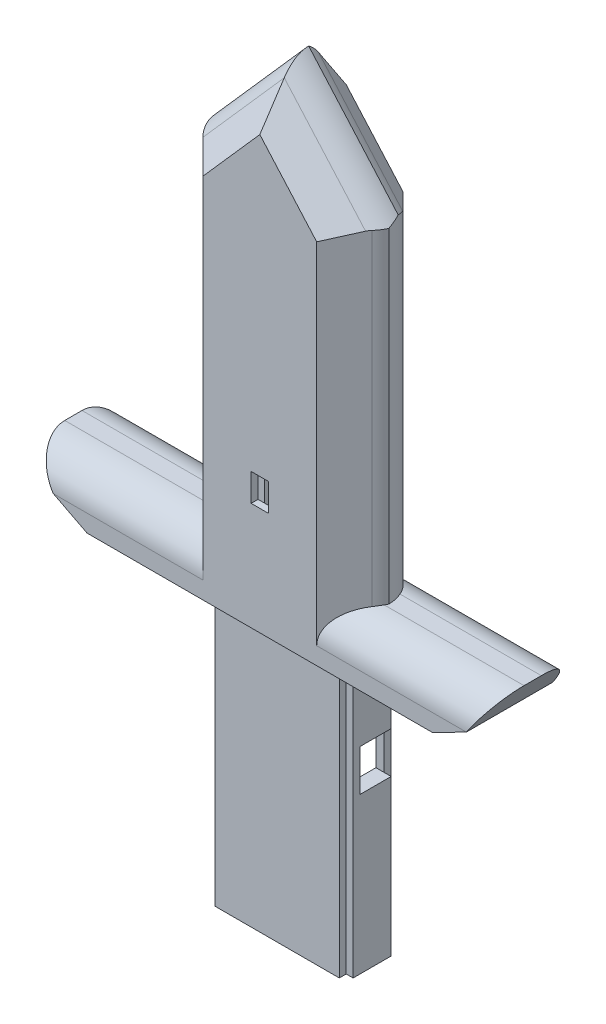
SolidWorks part; units mm, degrees
ref_plane "前视基准面" through (0, 0, 0) normal (0, 0, 1) x (1, 0, 0)
ref_plane "上视基准面" through (0, 0, 0) normal (0, 1, 0) x (1, 0, 0)
ref_plane "右视基准面" through (0, 0, 0) normal (1, 0, 0) x (0, 0, -1)
other "Configuration Table"
sketch "草图1" plane through (0, 0, 0) normal (0, 0, 1) x (1, 0, 0)
  line L0 (0, -55) -> (0, 55) construction
  line L1 (0, 200) -> (-26.4575, 170)
  line L2 (-26.4575, 170) -> (-26.4575, 75)
  line L3 (-26.4575, 75) -> (-66.4575, 75)
  line L4 (-66.4575, 75) -> (-59.7843, 65.0266)
  line L5 (-59.7843, 65.0266) -> (-50, 60)
  line L7 (-50, 60) -> (-20, 60)
  line L9 (-20, 60) -> (-20, -20)
  line L10 (-20, -20) -> (20, -20)
  line L11 (0, 200) -> (0, -20)
  line L15 (-26.4575, 170) -> (26.4575, 170) construction
  line L18 (20, 60) -> (20, -20)
  line L19 (50, 60) -> (20, 60)
  line L20 (59.7843, 65.0266) -> (50, 60)
  line L21 (66.4575, 75) -> (59.7843, 65.0266)
  line L22 (26.4575, 75) -> (66.4575, 75)
  line L23 (26.4575, 170) -> (26.4575, 75)
  line L24 (0, 200) -> (26.4575, 170)
  point P18 (0, 170)
  dimension "D1" = 80
  dimension "D2" = 20
  dimension "D3" = 220
  dimension "D4" = 40
  dimension "D5" = 95
  dimension "D6" = 15
  dimension "D7" = 30
  dimension "D8" = 40
  dimension "D9" = 12
  dimension "D10" = 11
  dimension "D11" = 20
extrude "凸台-拉伸1" add sketch "草图1" along normal blind 15 contours L1 L15 L11 | L11 L15 L24 | L15 L2 L3 L4 L5 L7 L9 L10 L11 | L15 L11 L10 L18 L19 L20 L21 L22 L23
sketch "草图2" plane through (0, 0, 0) normal (0, 0, -1) x (-1, 0, 0)
  line L0 (0, 81.7011) -> (-15, 66.7011)
  line L1 (-15, 66.7011) -> (0, 51.7011)
  line L2 (0, 51.7011) -> (15, 66.7011)
  line L3 (15, 66.7011) -> (0, 81.7011)
  dimension "D1" = 30
  dimension "D4" = 51.7011
extrude "切除-拉伸4" cut sketch "草图2" against normal through all
sketch "草图4" plane through (0, 0, 0) normal (0, 0, -1) x (-1, 0, 0)
  line L0 (-15, 66.7011) -> (-15, -15)
  line L1 (-15, -15) -> (15, -15)
  line L2 (15, -15) -> (15, 66.7011)
  line L3 (20, -20) -> (-20, -20) construction
  line M6 (15, 66.7011) -> (0, 51.7011)
  line M7 (0, 51.7011) -> (-15, 66.7011)
  dimension "D1" = 5
extrude "切除-拉伸5" cut sketch "草图4" against normal blind 5 and the other way through all contours L1 L2 L0 M6 M7
sketch "草图5" plane through (0, 0, 0) normal (0, 0, 1) x (1, 0, 0)
  line L0 (0, 200) -> (26.4575, 170)
  line L1 (26.4575, 170) -> (26.4575, 75)
  line L2 (26.4575, 75) -> (66.4575, 75)
  line L3 (66.4575, 75) -> (59.7843, 65.0266)
  line L4 (59.7843, 65.0266) -> (50, 60)
  line L5 (50, 60) -> (20, 60)
  line L6 (20, 60) -> (-20, 60)
  line L7 (-20, 60) -> (-50, 60)
  line L8 (-50, 60) -> (-59.7843, 65.0266)
  line L9 (-59.7843, 65.0266) -> (-66.4575, 75)
  line L10 (-66.4575, 75) -> (-26.4575, 75)
  line L11 (-26.4575, 75) -> (-26.4575, 170)
  line L12 (-26.4575, 170) -> (0, 200)
extrude "凸台-拉伸2" add sketch "草图5" against normal blind 5
sketch "草图7" plane through (0, 0, 0) normal (0, 0, 1) x (1, 0, 0)
  line L0 (0, 81.7011) -> (-15, 66.7011)
  line L1 (-15, 66.7011) -> (-15, 60)
  line L2 (-15, 60) -> (15, 60) construction
  line L3 (-15, 60) -> (15, 60)
  line L4 (15, 60) -> (15, 66.7011)
  line L5 (15, 66.7011) -> (0, 81.7011)
extrude "切除-拉伸6" cut sketch "草图7" against normal blind 5
sketch "草图8" plane through (0, 0, 5) normal (0, 0, -1) x (-1, 0, 0)
  line L0 (-15, 66.7011) -> (0, 51.7011)
  line L1 (0, 51.7011) -> (15, 66.7011)
  line L2 (15, 66.7011) -> (15, -15)
  line L3 (15, -15) -> (-15, -15)
  line L4 (-15, -15) -> (-15, 66.7011)
extrude "切除-拉伸7" cut sketch "草图8" against normal blind 5
sketch "草图9" plane through (0, -20, 0) normal (0, -1, 0) x (1, 0, 0)
  line L0 (15, 4) -> (15, 7)
  line L1 (15, 7) -> (-15, 7)
  line L2 (-15, 7) -> (-15, 4)
  line L3 (-15, 4) -> (15, 4)
  line L4 (-20, 0) -> (20, 0) construction
  line L5 (20, 15) -> (20, 0) construction
  line L6 (-20, 15) -> (-20, 0) construction
  line L7 (-20, 15) -> (20, 15) construction
  dimension "D1" = 4
  dimension "D2" = 5
  dimension "D3" = 5
  dimension "D4" = 8
extrude "切除-拉伸8" cut sketch "草图9" against normal blind 5
sketch "草图10" plane through (0, 0, -5) normal (0, 0, -1) x (-1, 0, 0)
  line L0 (-15, 66.7011) -> (-15, 116.7011)
  line L1 (-15, 116.7011) -> (15, 116.7011)
  line L2 (15, 116.7011) -> (15, 66.7011)
  line L3 (15, 66.7011) -> (-15, 66.7011)
  dimension "D1" = 50
extrude "切除-拉伸9" cut sketch "草图10" against normal up to surface (15 mm away) up to face at (0, 31.0207, 10)
sketch "草图11" plane through (0, 60, 0) normal (0, -1, 0) x (1, 0, 0)
  line L0 (17.5, -1.5) -> (15, -1.5)
  line L2 (15, -5) -> (15, 0) construction
  line L3 (15, -1.5) -> (15, -5)
  line L4 (15, -5) -> (-15, -5)
  line L5 (-15, -5) -> (-15, -1.5)
  line L6 (-15, -5) -> (-15, 0) construction
  line L7 (-15, -1.5) -> (-17.5, -1.5)
  line L8 (-17.5, -1.5) -> (-17.5, 0)
  line L9 (-20, 0) -> (-15, 0) construction
  line L10 (-17.5, 0) -> (17.5, 0)
  line L11 (17.5, 0) -> (17.5, -1.5)
  dimension "D1" = 1.5
  dimension "D2" = 1.5
  dimension "D3" = 2.5
  dimension "D4" = 2.5
extrude "切除-拉伸10" cut sketch "草图11" against normal up to surface (56.7011 mm away) up to face at (0, 116.7011, 2.5)
sketch "草图12" plane through (0, 0, 10) normal (0, 0, -1) x (-1, 0, 0)
sketch "草图13" plane through (0, 0, 10) normal (0, 0, -1) x (-1, 0, 0)
  line L0 (-20, 121.7011) -> (-20, 71.7011)
  line L1 (-20, 71.7011) -> (20, 71.7011)
  line L2 (20, 71.7011) -> (20.5279, 121.7011)
  line L3 (20.5279, 121.7011) -> (-20, 121.7011)
  dimension "D1" = 40
  dimension "D2" = 50
  dimension "D3" = 10
  dimension "D4" = 20
extrude "切除-拉伸11" cut sketch "草图13" along normal blind 7
sketch "草图14" plane through (0, 0, -5) normal (0, 0, -1) x (-1, 0, 0)
  line L0 (15, 116.7011) -> (-15, 116.7011) construction
  line L1 (-15.6, 116.7011) -> (15.6, 116.7011)
  line L2 (-15.6, 116.7011) -> (-15.6, -14.9949)
  line L3 (-15.6, -14.9949) -> (15.6, -14.9949)
  line L4 (15.6, 116.7011) -> (15.6, -14.9949)
  line L5 (-15, 60) -> (-15, 116.7011) construction
  line L6 (15, 116.7011) -> (15, 60) construction
  dimension "D1" = 0.6
  dimension "D2" = 0.6
  dimension "D3" = 131.6961
extrude "切除-拉伸12" cut sketch "草图14" against normal up to surface (15 mm away) up to face at (0, 31.0207, 10)
sketch "草图15" plane through (0, 71.7011, 0) normal (0, 1, 0) x (1, 0, 0)
  line L0 (-20, -10) -> (20, -10)
  line L1 (-20, -10) -> (-20, -3)
  line L2 (-20, -3) -> (-20, -10) construction
  line L3 (-20, -3) -> (20, -3)
  line L4 (20, -3) -> (20, -10)
  dimension "D1" = 7
extrude "切除-拉伸14" cut sketch "草图15" against normal blind 9
sketch "草图16" plane through (0, 0, 10) normal (0, 0, -1) x (-1, 0, 0)
  line L0 (0, 83.1153) -> (-16.4142, 66.7011)
  line L1 (-16.4142, 66.7011) -> (0, 50.2869)
  line L2 (0, 50.2869) -> (16.4142, 66.7011)
  line L3 (16.4142, 66.7011) -> (0, 83.1153)
  line L4 (-15, 66.7011) -> (0, 81.7011) construction
  line L5 (0, 81.7011) -> (15, 66.7011) construction
  line L6 (15, 66.7011) -> (0, 51.7011) construction
  line L7 (0, 51.7011) -> (-15, 66.7011) construction
  dimension "D1" = 1
  dimension "D2" = 1
  dimension "D3" = 1
  dimension "D4" = 1
extrude "切除-拉伸15" cut sketch "草图16" against normal through all
sketch "草图17" plane through (0, 0, 15) normal (0, 0, 1) x (1, 0, 0)
  line L0 (0, 83.1153) -> (-16.4142, 66.7011)
  line L1 (-16.4142, 66.7011) -> (0, 50.2869)
  line L2 (0, 50.2869) -> (16.4142, 66.7011)
  line L3 (16.4142, 66.7011) -> (0, 83.1153)
extrude "凸台-拉伸3" add sketch "草图17" against normal up to surface (5 mm away) up to face at (0, 66.7011, 10)
sketch "草图18" plane through (0, 0, 15) normal (0, 0, 1) x (1, 0, 0)
  line L0 (-20, 60) -> (20, 60)
  line L1 (20, 60) -> (20, -20)
  line L2 (20, -20) -> (-20, -20)
  line L3 (-20, -20) -> (-20, 60)
sketch "草图19" plane through (0, 0, 15) normal (0, 0, 1) x (1, 0, 0)
  line L0 (-26.4575, 75) -> (26.4575, 75)
  line L1 (0, 200) -> (0, 75)
sketch "草图23" plane through (-26.4575, 0, 0) normal (-1, 0, 0) x (0, 0, 1)
  line L0 (-5, 75) -> (15, 75)
  line L1 (5, 75) -> (5, 82.7603) construction
sketch "草图24" plane through (26.4575, 0, 0) normal (1, 0, 0) x (0, 0, -1)
  line L0 (-15, 75) -> (5, 75)
  line L1 (-5, 75) -> (-5, 85.0123) construction
sketch "草图26" plane through (0, 0, 15) normal (0, 0, 1) x (1, 0, 0)
  line L0 (0, 200) -> (-26.4575, 170)
  line L1 (-26.4575, 170) -> (-26.4575, 75)
  line L2 (-26.4575, 75) -> (-66.4575, 75)
  line L3 (-66.4575, 75) -> (-59.7843, 65.0266)
  line L4 (-59.7843, 65.0266) -> (-50, 60)
  line L5 (-50, 60) -> (-20, 60)
  line L6 (-20, 60) -> (50, 60)
  line L7 (50, 60) -> (59.7843, 65.0266)
  line L8 (59.7843, 65.0266) -> (66.4575, 75)
  line L9 (66.4575, 75) -> (26.4575, 75)
  line L10 (26.4575, 75) -> (26.4575, 170)
  line L11 (26.4575, 170) -> (0, 200)
extrude "凸台-拉伸4" add sketch "草图26" along normal blind 5
sketch "草图27" plane through (0, -20, 0) normal (0, -1, 0) x (1, 0, 0)
  line L2 (-20, 15) -> (-18, 15)
  line L3 (20, 15) -> (-20, 15) construction
  line L4 (-18, 15) -> (-18, 13)
  line L5 (-18, 13) -> (-20, 13)
  line L6 (-20, 15) -> (-20, 0) construction
  line L7 (-20, 13) -> (-20, 15)
  line L8 (-20, 0) -> (-18, 0)
  line L9 (-20, 0) -> (20, 0) construction
  line L10 (-18, 0) -> (-18, 2)
  line L11 (-18, 2) -> (-20, 2)
  line L12 (-20, 2) -> (-20, 0)
  line L13 (20, 15) -> (20, 13)
  line L14 (20, 15) -> (20, 0) construction
  line L15 (20, 13) -> (18, 13)
  line L16 (18, 13) -> (18, 15)
  line L17 (18, 15) -> (20, 15)
  line L18 (20, 0) -> (18, 0)
  line L19 (18, 0) -> (18, 2)
  line L20 (18, 2) -> (20, 2)
  line L21 (20, 2) -> (20, 0)
  dimension "D1" = 2
  dimension "D2" = 2
  dimension "D3" = 2
  dimension "D4" = 2
  dimension "D5" = 2
  dimension "D6" = 2
  dimension "D7" = 2
  dimension "D8" = 2
extrude "切除-拉伸17" cut sketch "草图27" against normal blind 80
sketch "草图29" plane through (0, -20, 0) normal (0, -1, 0) x (-1, 0, 0)
  line L0 (15, -7) -> (15, -4)
  line L1 (15, -4) -> (-15, -4)
  line L2 (-15, -4) -> (-15, -7)
  line L3 (-15, -7) -> (15, -7)
extrude "凸台-拉伸5" add sketch "草图29" against normal up to surface (5 mm away) up to face at (0, -15, 8.5)
sketch "草图30" plane through (15.6, 0, 0) normal (-1, 0, 0) x (0, 0, 1)
  line L0 (2, 25.0051) -> (10, 25.0051)
  line L2 (10, -14.9949) -> (10, 62.7011) construction
  line L3 (10, 25.0051) -> (10, 37.0051)
  line L4 (10, 37.0051) -> (2, 37.0051)
  line L5 (2, 37.0051) -> (2, 25.0051)
  line L6 (10, -14.9949) -> (0, -14.9949) construction
  dimension "D1" = 40
  dimension "D2" = 12
  dimension "D3" = 8
extrude "切除-拉伸19" cut sketch "草图30" against normal up to surface (4.4 mm away) up to face at (20, 20, 7.5)
sketch "草图31" plane through (15.6, 0, 0) normal (-1, 0, 0) x (0, 0, 1)
  line L0 (10, 35.0051) -> (2, 35.0051)
  line L1 (10, 37.0051) -> (10, 62.7011) construction
  line L2 (2, 35.0051) -> (2, 44.0051)
  line L3 (2, 44.0051) -> (10, 44.0051)
  line L4 (10, 44.0051) -> (10, 35.0051)
  line L5 (10, -14.9949) -> (0, -14.9949) construction
  dimension "D1" = 8
  dimension "D2" = 50
  dimension "D3" = 9
sketch "草图32" plane through (0, 60, 0) normal (0, -1, 0) x (1, 0, 0)
  line L0 (-18, 15) -> (18, 15) construction
  line L1 (-22.4, 17.4) -> (22.4, 17.4)
  line L2 (-22.4, 17.4) -> (-22.4, -2.4)
  line L3 (-22.4, -2.4) -> (22.4, -2.4)
  line L4 (22.4, 17.4) -> (22.4, -2.4)
  line L5 (-20, 13) -> (-20, 2) construction
  dimension "D1" = 44.8
  dimension "D2" = 19.8
  dimension "D3" = 2.4
  dimension "D4" = 2.4
extrude "切除-拉伸21" cut sketch "草图32" against normal blind 5
sketch "草图35" plane through (0, 65, 0) normal (0, -1, 0) x (1, 0, 0)
  line L0 (-50, 20) -> (50, 20)
  line L1 (50, 20) -> (50, -5)
  line L2 (50, -5) -> (-50, -5)
  line L3 (-50, -5) -> (-50, 20)
  line L5 (25, -1.5) -> (-25, -1.5)
  line L6 (25, -1.5) -> (25, 16.5)
  line L7 (25, 16.5) -> (-25, 16.5)
  line L8 (-25, -1.5) -> (-25, 16.5)
  line L11 (20, 10) -> (20, 3) construction
  line L13 (15.5816, -5) -> (15.6, -1.5)
  line L14 (-15.6, -5) -> (-15.6, -1.5)
  line M6 (-15.6, -5) -> (-15.6, -1.5)
  line M7 (-15.6, -1.5) -> (-17.5, -1.5)
  line M27 (17.5, -1.5) -> (15.6, -1.5)
  line M28 (15.6, -1.5) -> (15.6, -5)
  line M29 (15.6, -5) -> (50, -5)
  line M30 (50, -5) -> (50, 20)
  line M31 (50, 20) -> (-50, 20)
  line M32 (-50, 20) -> (-50, -5)
  line M33 (-50, -5) -> (-15.6, -5)
  dimension "D1" = 18
  dimension "D2" = 3.5
  dimension "D3" = 50
  dimension "D4" = 5
extrude "凸台-拉伸7" add sketch "草图35" along normal blind 5 contours L5 L8 L7 L6 M27 M28 M29 M30 M31 M32 M33 M6 M7
sketch "草图36" plane through (0, 65, 0) normal (0, -1, 0) x (1, 0, 0)
  line L0 (25, -1.5) -> (25, 16.5)
  line L1 (25, 16.5) -> (-25, 16.5)
  line L2 (-25, 16.5) -> (-25, -1.5)
  line L3 (-25, -1.5) -> (25, -1.5)
  line M1 (-25, 16.5) -> (-25, -1.5)
  line M2 (-25, -1.5) -> (-17.5, -1.5)
  line M3 (-17.5, -1.5) -> (-17.5, 0)
  line M4 (-17.5, 0) -> (-18, 0)
  line M5 (-18, 0) -> (-18, 2)
  line M6 (-18, 2) -> (-20, 2)
  line M7 (-20, 2) -> (-20, 3)
  line M8 (-20, 3) -> (-20, 10)
  line M9 (-20, 10) -> (-20, 13)
  line M10 (-20, 13) -> (-18, 13)
  line M11 (-18, 13) -> (-18, 15)
  line M12 (-18, 15) -> (18, 15)
  line M13 (18, 15) -> (18, 13)
  line M14 (18, 13) -> (20, 13)
  line M15 (20, 13) -> (20, 10)
  line M16 (20, 10) -> (20, 3)
  line M17 (20, 3) -> (20, 2)
  line M18 (20, 2) -> (18, 2)
  line M19 (18, 2) -> (18, 0)
  line M20 (18, 0) -> (17.5, 0)
  line M21 (17.5, 0) -> (17.5, -1.5)
  line M22 (17.5, -1.5) -> (25, -1.5)
  line M23 (25, -1.5) -> (25, 16.5)
  line M24 (25, 16.5) -> (-25, 16.5)
extrude "凸台-拉伸9" add sketch "草图36" along normal blind 2 contours M24 M1 M2 M3 M4 M5 M6 M7 M8 M9 M10 M11 M12 M13 M14 M15 M16 M17 M18 M19 M20 M21 M22 M23
sketch "草图37" plane through (0, 63, 0) normal (0, -1, 0) x (-1, 0, 0)
  line L0 (25, -16.5) -> (25, 1.5) construction
  line L1 (-25, -16.5) -> (25, -16.5) construction
  line L2 (25, 1.5) -> (17.5, 1.5) construction
  line L3 (-25, 1.5) -> (-25, -16.5) construction
  line L4 (-25, -16.5) -> (25, -16.5) construction
  line L5 (-17.5, 1.5) -> (-25, 1.5) construction
  circle A0 centre (22.5, -14) radius 1.2
  circle A1 centre (-22.5, -14) radius 1.2
  circle A2 centre (-22.5, -1) radius 1.2
  circle A3 centre (22.5, -1) radius 1.2
  dimension "D1" = 2.4
  dimension "D4" = 2.4
  dimension "D10" = 2.4
  dimension "D11" = 2.4
  dimension "D2" = 2.5
  dimension "D3" = 2.5
  dimension "D5" = 2.5
  dimension "D6" = 2.5
  dimension "D7" = 2.5
  dimension "D8" = 2.5
  dimension "D9" = 2.5
  dimension "D12" = 2.5
chamfer "倒角1" distance 10 angle 45 1 edges at (-13.2288, 185, -5)
chamfer "倒角2" distance 10 angle 45 1 edges at (16.5621, 181.2204, -5)
chamfer "倒角3" distance 10 angle 45 1 edges at (13.2288, 185, 20)
chamfer "倒角4" distance 10 angle 45 1 edges at (-16.5621, 181.2204, 20)
chamfer "倒角5" distance 10 angle 45 1 edges at (26.4575, 114.9407, 20)
chamfer "倒角6" distance 10 angle 45 1 edges at (26.4575, 114.9407, -5)
chamfer "倒角7" distance 10 angle 45 1 edges at (-26.4575, 114.9407, -5)
chamfer "倒角8" distance 10 angle 45 1 edges at (-26.4575, 114.9407, 20)
fillet "圆角7" radius 10 1 edges at (41.4575, 75, 20)
fillet "圆角8" radius 10 1 edges at (41.4575, 75, -5)
fillet "圆角9" radius 10 1 edges at (-41.4575, 75, -5)
fillet "圆角10" radius 10 1 edges at (-41.4575, 75, 20)
fillet "圆角11" radius 10 1 edges at (26.4575, 122.5, 5)
fillet "圆角12" radius 10 1 edges at (26.4575, 122.5, 10)
fillet "圆角14" radius 10 1 edges at (13.0034, 185.2555, 10)
fillet "圆角15" radius 10 1 edges at (12.7797, 185.5092, 5)
fillet "圆角16" radius 10 1 edges at (-13.5282, 184.6605, 10)
fillet "圆角17" radius 10 1 edges at (-13.379, 184.8296, 5)
fillet "圆角18" radius 10 1 edges at (-26.4575, 121.821, 10)
fillet "圆角19" radius 10 1 edges at (-26.4575, 122.1593, 5)
sketch "草图38" plane through (0, 0, 10) normal (0, 0, -1) x (-1, 0, 0)
  line L2 (15.6, 62.7011) -> (15.6, -14.9949) construction
  line L3 (-15, -15) -> (15, -15) construction
  circle A0 centre (-11.9, 20.2) radius 1.2
  circle A1 centre (12.3, 20.2) radius 1.2
  circle A2 centre (12.3, 57) radius 1.2
  circle A3 centre (-11.9, 57) radius 1.2
  dimension "D1" = 2.4
  dimension "D2" = 2.4
  dimension "D3" = 2.4
  dimension "D4" = 2.4
  dimension "D5" = 24.2
  dimension "D6" = 24.2
  dimension "D7" = 3.3
  dimension "D8" = 3.3
  dimension "D9" = 35.2
  dimension "D10" = 35.2
  dimension "D11" = 72
  dimension "D12" = 72
extrude "切除-拉伸23" cut sketch "草图38" against normal blind 3
sketch "草图39" plane through (0, 0, 10) normal (0, 0, -1) x (-1, 0, 0)
  line L0 (-15.6, -14.9949) -> (-15.6, 81.8297)
  line L1 (-15.6, 81.8297) -> (15.6, 81.8297)
  line L2 (15.6, 81.8297) -> (15.6, -14.9949)
  line L3 (15.6, -14.9949) -> (-15.6, -14.9949)
sketch "草图40" plane through (0, 121.7011, 0) normal (0, -1, 0) x (1, 0, 0)
  line L1 (-25.4676, 12.5781) -> (26.0169, 12.5781)
  line L2 (-25.4676, 12.5781) -> (-25.4676, 0.933)
  line L3 (-25.4676, 0.933) -> (26.0169, 0.933)
  line L4 (26.0169, 12.5781) -> (26.0169, 0.933)
  line M5 (20, 10) -> (-20.5279, 10)
  line M6 (-20.5279, 10) -> (-20.5279, 3)
  line M7 (-20.5279, 3) -> (20, 3)
  line M8 (20, 3) -> (20, 10)
extrude "切除-拉伸24" cut sketch "草图40" against normal blind 8 contours M8 M5 M6 M7
sketch "草图41" plane through (0, 116.7011, 0) normal (0, -1, 0) x (1, 0, 0)
  line L1 (21.831, -9.4178) -> (-23.2428, -9.4178)
  line L2 (21.831, -9.4178) -> (21.831, 6.3066)
  line L3 (21.831, 6.3066) -> (-23.2428, 6.3066)
  line L4 (-23.2428, -9.4178) -> (-23.2428, 6.3066)
  line M5 (-15.6, -5) -> (15.6, -5)
  line M6 (15.6, -5) -> (15.6, -1.5)
  line M7 (15.6, -1.5) -> (17.5, -1.5)
  line M8 (17.5, -1.5) -> (17.5, 0)
  line M9 (17.5, 0) -> (15.6, 0)
  line M10 (15.6, 0) -> (15.6, 3)
  line M11 (15.6, 3) -> (-15.6, 3)
  line M12 (-15.6, 3) -> (-15.6, 0)
  line M13 (-15.6, 0) -> (-17.5, 0)
  line M14 (-17.5, 0) -> (-17.5, -1.5)
  line M15 (-17.5, -1.5) -> (-15.6, -1.5)
  line M16 (-15.6, -1.5) -> (-15.6, -5)
extrude "切除-拉伸25" cut sketch "草图41" against normal blind 46 contours M16 M5 M6 M7 M8 M9 M10 M11 M12 M13 M14 M15
sketch "草图42" plane through (0, 129.7011, 0) normal (0, -1, 0) x (1, 0, 0)
  line L1 (-35.652, 24.0881) -> (44.2679, 24.0881)
  line L2 (-35.652, 24.0881) -> (-35.652, -20.2789)
  line L3 (-35.652, -20.2789) -> (44.2679, -20.2789)
  line L4 (44.2679, 24.0881) -> (44.2679, -20.2789)
  line M5 (20, 3) -> (20, 10)
  line M6 (20, 10) -> (-20.5279, 10)
  line M7 (-20.5279, 10) -> (-20.5279, 3)
  line M8 (-20.5279, 3) -> (-15.6, 3)
  line M9 (-15.6, 3) -> (15.6, 3)
  line M10 (15.6, 3) -> (20, 3)
extrude "切除-拉伸26" cut sketch "草图42" against normal up to surface (33 mm away) contours M10 M5 M6 M7 M8 M9 up to face at (0, 162.7011, -0.8333)
sketch "草图43" plane through (0, 0, 10) normal (0, 0, -1) x (-1, 0, 0)
  line L0 (-15.6, 15.2) -> (15.6, 15.2)
  line L1 (-10.6, 106.2) -> (10.6, 106.2)
  line L2 (-10.6, 106.2) -> (-10.6, 84.2)
  line L3 (-10.6, 84.2) -> (10.6, 84.2)
  line L4 (10.6, 106.2) -> (10.6, 84.2)
  line L5 (-15.6, -14.9949) -> (-15.6, 25.0051) construction
  line L6 (15.6, 62.7011) -> (15.6, -14.9949) construction
  line L7 (-15.6, 37.0051) -> (-15.6, 62.7011) construction
  circle A0 centre (-11.9, 20.2) radius 1.2 construction
  dimension "D1" = 5
  dimension "D2" = 69
  dimension "D3" = 91
  dimension "D4" = 5
  dimension "D5" = 5
extrude "切除-拉伸27" cut sketch "草图43" against normal up to surface (10 mm away) contours L4 L1 L2 L3 up to face at (0, 99.7025, 20)
sketch "草图46" plane through (0, 60, 0) normal (0, -1, 0) x (1, 0, 0)
  line L1 (-27.4, 17.4) -> (27.4, 17.4)
  line L2 (-27.4, 17.4) -> (-27.4, -2.4)
  line L3 (-27.4, -2.4) -> (27.4, -2.4)
  line L4 (27.4, 17.4) -> (27.4, -2.4)
  line L6 (-20, 10) -> (-20, 13) construction
  line L8 (-18, 15) -> (18, 15) construction
  line M5 (-15.6, -1.5) -> (-25, -1.5)
  line M6 (-25, -1.5) -> (-25, 16.5)
  line M7 (-25, 16.5) -> (25, 16.5)
  line M8 (25, 16.5) -> (25, -1.5)
  line M9 (25, -1.5) -> (15.6, -1.5)
  line M10 (15.6, -1.5) -> (15.6, -5)
  line M16 (-15.6, -5) -> (-15.6, -1.5)
  dimension "D1" = 19.8
  dimension "D2" = 54.8
  dimension "D3" = 7.4
  dimension "D4" = 2.4
extrude "切除-拉伸28" cut sketch "草图46" against normal up to surface (3 mm away) contours L4 L1 L2 L3 M16 M5 M6 M7 M8 M9 M10 up to face at (0, 63, 5.9583)
sketch "草图47" plane through (0, 63, 0) normal (0, -1, 0) x (1, 0, 0)
  line L0 (27.4, 17.4) -> (-27.4, 17.4) construction
  line L1 (-27.4, -2.4) -> (-27.4, 17.4) construction
  line L3 (-15.6, -2.4) -> (-27.4, -2.4) construction
  line L4 (27.4, -2.4) -> (27.4, 17.4) construction
  line L5 (27.4, -2.4) -> (15.6, -2.4) construction
  line L6 (27.4, 17.4) -> (27.4, -2.4) construction
  circle A0 centre (-24.9, 14.9) radius 1.2
  circle A1 centre (24.9, 14.9) radius 1.2
  circle A2 centre (24.9, 0.1) radius 1.2
  circle A3 centre (-24.9, 0.1) radius 1.2
  dimension "D3" = 2.4
  dimension "D6" = 2.4
  dimension "D9" = 2.4
  dimension "D12" = 2.4
  dimension "D1" = 2.5
  dimension "D2" = 2.5
  dimension "D4" = 2.5
  dimension "D5" = 2.5
  dimension "D7" = 2.5
  dimension "D8" = 2.5
  dimension "D10" = 2.5
  dimension "D11" = 2.5
extrude "切除-拉伸29" cut sketch "草图47" against normal blind 3
sketch "草图48" plane through (0, 62.7011, 0) normal (0, 1, 0) x (1, 0, 0)
  line L1 (-26.5409, 2.5519) -> (32.582, 2.5519)
  line L2 (-26.5409, 2.5519) -> (-26.5409, -20.82)
  line L3 (-26.5409, -20.82) -> (32.582, -20.82)
  line L4 (32.582, 2.5519) -> (32.582, -20.82)
  line M1 (-15.6, -3) -> (-20, -3)
  line M2 (-20, -3) -> (-20, -10)
  line M3 (-20, -10) -> (-15.6, -10)
  line M4 (-15.6, -10) -> (-15.6, -3)
extrude "凸台-拉伸10" add sketch "草图48" along normal blind 9 contours M4 M1 M2 M3
sketch "草图49" plane through (0, 62.7011, 0) normal (0, 1, 0) x (1, 0, 0)
  line L1 (8.4178, 4.2355) -> (27.2342, 4.2355)
  line L2 (8.4178, 4.2355) -> (8.4178, -17.2548)
  line L3 (8.4178, -17.2548) -> (27.2342, -17.2548)
  line L4 (27.2342, 4.2355) -> (27.2342, -17.2548)
  line M1 (15.6, -10) -> (20, -10)
  line M2 (20, -10) -> (20, -3)
  line M3 (20, -3) -> (15.6, -3)
  line M4 (15.6, -3) -> (15.6, -10)
extrude "凸台-拉伸11" add sketch "草图49" along normal blind 9 contours M4 M1 M2 M3
sketch "草图50" plane through (0, 0, 10) normal (0, 0, -1) x (-1, 0, 0)
  line L1 (-63.6393, 193.626) -> (75.0944, 193.626)
  line L2 (-63.6393, 193.626) -> (-63.6393, -29.1115)
  line L3 (-63.6393, -29.1115) -> (75.0944, -29.1115)
  line L4 (75.0944, 193.626) -> (75.0944, -29.1115)
  circle M5 centre (-11.9, 57) radius 1.2
  circle M6 centre (12.3, 57) radius 1.2
  circle M7 centre (12.3, 20.2) radius 1.2
  circle M8 centre (-11.9, 20.2) radius 1.2
  line M9 (-10.6, 106.2) -> (10.6, 106.2)
  line M10 (10.6, 106.2) -> (10.6, 84.2)
  line M11 (10.6, 84.2) -> (-10.6, 84.2)
  line M12 (-10.6, 84.2) -> (-10.6, 106.2)
  line M13 (-20, 71.7011) -> (-15.6, 71.7011)
  line M14 (-15.6, 71.7011) -> (-15.6, 37.0051)
  line M15 (-15.6, 37.0051) -> (-20, 37.0051)
  line M16 (-20, 37.0051) -> (-20, 25.0051)
  line M17 (-20, 25.0051) -> (-15.6, 25.0051)
  line M18 (-15.6, 25.0051) -> (-15.6, -14.9949)
  line M19 (-15.6, -14.9949) -> (-15, -14.9949)
  line M20 (-15, -14.9949) -> (-15, -15)
  line M21 (-15, -15) -> (15, -15)
  line M22 (15, -15) -> (15, -14.9949)
  line M23 (15, -14.9949) -> (15.6, -14.9949)
  line M24 (15.6, -14.9949) -> (15.6, 71.7011)
  line M25 (15.6, 71.7011) -> (20, 71.7011)
  line M26 (20, 71.7011) -> (20.5279, 121.7011)
  line M27 (20.5279, 121.7011) -> (20.5279, 162.7011)
  line M28 (20.5279, 162.7011) -> (-20, 162.7011)
  line M29 (-20, 162.7011) -> (-20, 71.7011)
extrude "切除-拉伸30" cut sketch "草图50" against normal blind 1 contours M29 M13 M14 M15 M16 M17 M18 M19 M20 M21 M22 M23 M24 M25 M26 M27 M28 M6 M8 M12 M9 M10 M11 M7 M5
sketch "草图52" plane through (0, 0, 20) normal (0, 0, 1) x (1, 0, 0)
  line L0 (-2.5, 99.2) -> (-2.5, 91.2)
  line L1 (-2.5, 91.2) -> (2.5, 91.2)
  line L2 (2.5, 91.2) -> (2.5, 99.2)
  line L3 (2.5, 99.2) -> (-2.5, 99.2)
  line L6 (10.6, 106.2) -> (-10.6, 106.2) construction
  line L7 (-10.6, 106.2) -> (-10.6, 84.2) construction
  line M12 (10.6, 84.2) -> (-10.6, 84.2)
  line M13 (-10.6, 84.2) -> (-10.6, 106.2)
  line M14 (-10.6, 106.2) -> (10.6, 106.2)
  line M15 (10.6, 106.2) -> (10.6, 84.2)
  dimension "D1" = 5
  dimension "D2" = 8
  dimension "D3" = 7
  dimension "D4" = 8.1
extrude "凸台-拉伸12" add sketch "草图52" against normal blind 2 contours L3 L2 L1 L0 M12 M15 M14 M13
sketch "草图53" plane through (0, 0, 11) normal (0, 0, -1) x (-1, 0, 0)
  line L0 (-10, 79.2) -> (-10, 61.2)
  line L1 (-10, 61.2) -> (10, 61.2)
  line L2 (10, 61.2) -> (10, 79.2)
  line L3 (10, 79.2) -> (-10, 79.2)
  line L4 (-15.6, 71.7011) -> (-15.6, 37.0051) construction
  line L6 (10.6, 84.2) -> (-10.6, 84.2) construction
  dimension "D1" = 20
  dimension "D2" = 18
  dimension "D3" = 5.6
  dimension "D4" = 5
extrude "切除-拉伸31" cut sketch "草图53" against normal blind 2
sketch "草图54" plane through (0, 162.7011, 0) normal (0, -1, 0) x (1, 0, 0)
  line L0 (-15.6, 3) -> (15.6, 3)
  line L2 (-27.0309, 16.3139) -> (27.2462, 16.3139)
  line L3 (-27.0309, 16.3139) -> (-27.0309, 0.5752)
  line L4 (-27.0309, 0.5752) -> (27.2462, 0.5752)
  line L5 (27.2462, 16.3139) -> (27.2462, 0.5752)
  line M9 (15.6, 3) -> (20, 3)
  line M10 (20, 3) -> (20, 11)
  line M11 (20, 11) -> (-20.5279, 11)
  line M12 (-20.5279, 11) -> (-20.5279, 3)
  line M13 (-20.5279, 3) -> (-15.6, 3)
extrude "切除-拉伸33" cut sketch "草图54" against normal blind 6 contours L0 M13 M9 M10 M11 M12
